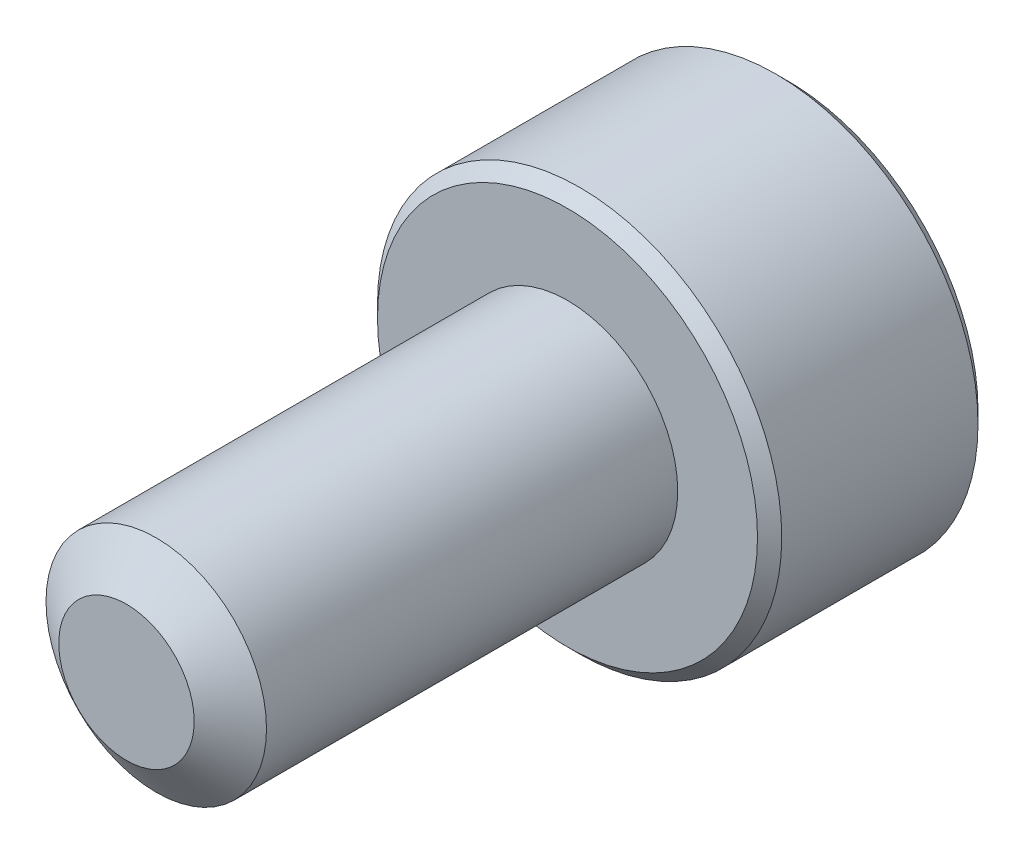
SolidWorks part; units mm, degrees
ref_plane "Front Plane" through (0, 0, 0) normal (0, 0, 1) x (1, 0, 0)
ref_plane "Top Plane" through (0, 0, 0) normal (0, 1, 0) x (1, 0, 0)
ref_plane "Right Plane" through (0, 0, 0) normal (1, 0, 0) x (0, 0, -1)
sketch "Sketch1" plane through (0, 0, 0) normal (0, 0, 1) x (1, 0, 0)
  circle A0 centre (0, 0) radius 1.5
  dimension "OD" = 3
extrude "Extrude1" add sketch "Sketch1" against normal blind 6
sketch "Sketch2" plane through (0, 0, 0) normal (0, 0, 1) x (1, 0, 0)
  circle A0 centre (0, 0) radius 1.5 construction
  circle A1 centre (0, 0) radius 1.5
curve "Helix/Spiral1" [suppressed] pitch 0.5 height 6.5 turns 13 parameters "pitch"=0.5
sketch "Sketch3" plane through (0, 0, 0) normal (1, 0, 0) x (0, 0, -1)
  line L0 (-0.4375, 1.5) -> (-0.25, 1.1752)
  line L1 (-0.25, 1.1752) -> (-0.1875, 1.1752)
  line L2 (-0.1875, 1.1752) -> (0, 1.5)
  line L3 (-0.4375, 1.5) -> (0, 1.5)
  line L4 (-0.2188, 1.5) -> (-0.2188, 1.1752) construction
  line L5 (-0.3438, 1.3376) -> (-0.0938, 1.3376) construction
  line L6 (0, 1.5) -> (0, -1.5) construction
  line L7 (0, -1.5) -> (6, -1.5) construction
  point P11 (2.25, -1.5)
  dimension "D1" = 0.0625
  dimension "D2" = 0.25
  dimension "D3" = 60
  dimension "D4" = 2.25
sweep "Cut-Sweep1" [suppressed] cut profiles "Sketch3" path "Helix/Spiral1"
sketch "Sketch4" plane through (0, 0, 0) normal (1, 0, 0) x (0, 0, -1)
  line L0 (0.4053, 1.5) -> (0, 0.9212)
  line L1 (0, 0.9212) -> (0, 1.5)
  line L2 (0.4053, 1.5) -> (0, 1.5)
  line L3 (-0.4375, 1.5) -> (0, 1.5) construction
  line L4 (0, 0) -> (7.0209, 0) construction
  dimension "D1" = 55
  dimension "D2" = 0.254
revolve "Cut-Revolve1" cut sketch "Sketch4" angle 360 about L4
sketch "Sketch5" [suppressed] plane through (0, 0, 0) normal (1, 0, 0) x (0, 0, -1)
  line L0 (6, -1.1822) -> (6, 1.0703) construction
  line L1 (6, 1.5) -> (0.1203, 1.5)
  line L2 (6, 1.5) -> (6, 0)
  line L3 (6, 0) -> (0.0001, 0)
  line L4 (0.0001, 1.1698) -> (0.0001, 0)
  line L5 (0.1203, 1.5) -> (0.0001, 1.1698)
  line L6 (0, 0) -> (9.9695, 0) construction
  point P3 (0.0001, 1.5)
  point P10 (0.0001, 1.5)
  dimension "D1" = 0.3302
  dimension "Thread min" = 0.0001
  dimension "D3" = 20
revolve "partially thread" [suppressed] add sketch "Sketch5" angle 360 about L6
sketch "Sketch6" plane through (0, 0, -6) normal (0, 0, -1) x (-1, 0, 0)
  circle A0 centre (0, 0) radius 2.75
  dimension "head dia" = 5.5
extrude "Extrude2" add sketch "Sketch6" along normal blind 3
sketch "Sketch7" plane through (0, 0, -9) normal (0, 0, -1) x (-1, 0, 0)
  line L1 (0, 1.4434) -> (-1.25, 0.7217)
  line L2 (-1.25, 0.7217) -> (-1.25, -0.7217)
  line L3 (-1.25, -0.7217) -> (0, -1.4434)
  line L4 (0, -1.4434) -> (1.25, -0.7217)
  line L5 (1.25, -0.7217) -> (1.25, 0.7217)
  line L6 (1.25, 0.7217) -> (0, 1.4434)
  circle A0 centre (0, 0) radius 1.25 construction
  dimension "hex dia" = 2.5
extrude "Cut-Extrude1" cut sketch "Sketch7" against normal blind 1.875
sketch "Sketch8" plane through (0, 0, -9) normal (0, 0, -1) x (-1, 0, 0)
  circle A0 centre (0, 0) radius 1.4434
extrude "Cut-Extrude2" cut sketch "Sketch8" against normal through all draft 45
chamfer "Chamfer1" distance 0.165 angle 45 2 edges at (-2.75, 0, -9) (-2.75, 0, -6)
sketch "Sketch9" plane through (0, 0, 0) normal (1, 0, 0) x (0, 0, -1)
  line L0 (0, 1.5) -> (0, -1.5) construction
  line L1 (2.75, 1.5) -> (2.75, -1.5) construction
  dimension "D1" = 2.75
sketch "Sketch10" plane through (0, 0, 0) normal (1, 0, 0) x (0, 0, -1)
  line L0 (6, 1.5) -> (6, 0)
  line L1 (6, 1.5) -> (5.875, 1.5)
  line L2 (5.875, 1.5) -> (5.2537, 0)
  line L3 (6, 0) -> (5.2537, 0)
  line L4 (6, 2.585) -> (6, -2.585) construction
  dimension "D1" = 22.5
  dimension "D2" = 0.125
revolve "Revolve1" add sketch "Sketch10" angle 360 about L3
equation "\"D3@Helix/Spiral1\" = \"screw length@Extrude1\"+\"pitch@Helix/Spiral1\""
equation "\"D1@Sketch3\" = \"pitch@Helix/Spiral1\"*.125"
equation "\"D2@Sketch3\" = \"pitch@Helix/Spiral1\"*.5"
equation "\"D1@Cut-Extrude1\" = \"hex dia@Sketch7\"*.75"
equation "\"D1@Chamfer1\" = \"head dia@Sketch6\"*.03"
equation "\"D1@Sketch9\" = \"pitch@Helix/Spiral1\"*5.5"
equation "\"D2@Sketch10\" = \"pitch@Helix/Spiral1\"*.25"
equation "\"D4@Sketch3\" = \"pitch@Helix/Spiral1\"*4.50"
